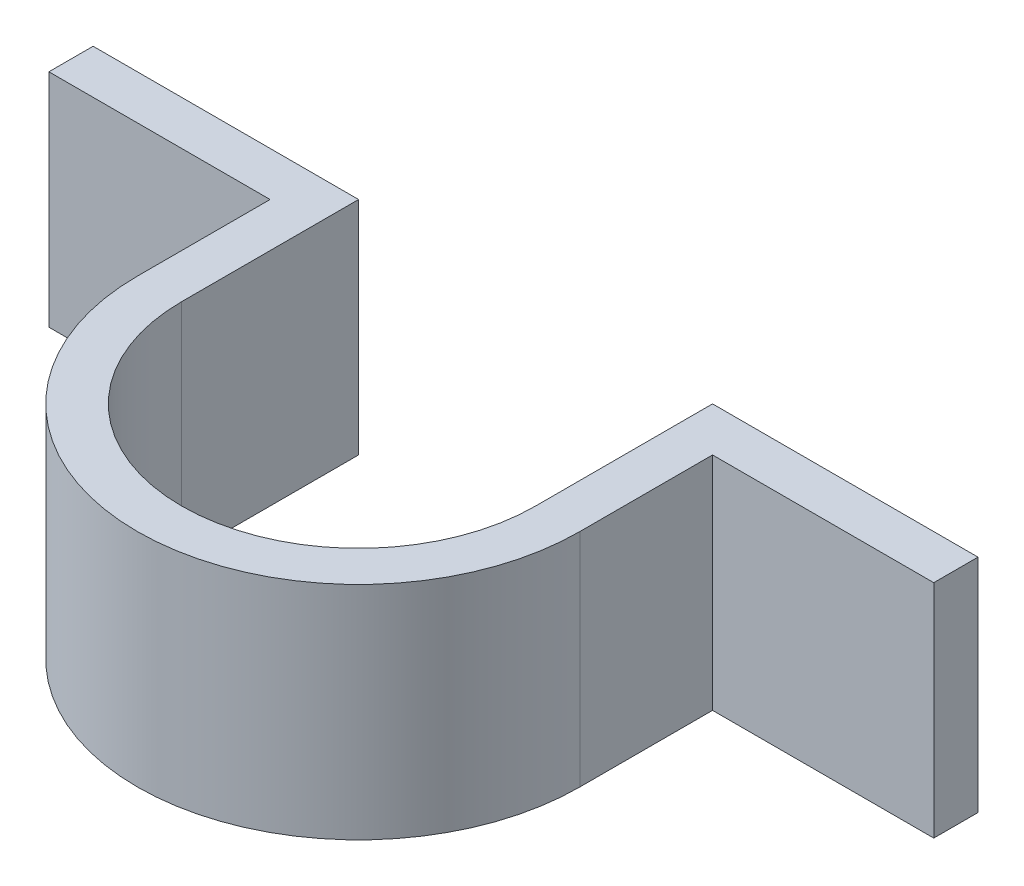
SolidWorks part; units mm, degrees
ref_plane "Front Plane" through (0, 0, 0) normal (0, 0, 1) x (1, 0, 0)
ref_plane "Top Plane" through (0, 0, 0) normal (0, 1, 0) x (1, 0, 0)
ref_plane "Right Plane" through (0, 0, 0) normal (1, 0, 0) x (0, 0, -1)
sketch "Sketch1" plane through (0, 0, 0) normal (0, 1, 0) x (1, 0, 0)
  line L0 (-4, 0) -> (-4, 4)
  line L1 (-4, 4) -> (-10, 4)
  line L6 (-10, 4) -> (-10, 3)
  line L7 (-10, 3) -> (-5, 3)
  line L10 (-5, 3) -> (-5, 0)
  line L11 (4, 0) -> (4, 4)
  line L12 (4, 4) -> (10, 4)
  line L13 (10, 4) -> (10, 3)
  line L14 (10, 3) -> (5, 3)
  line L15 (5, 3) -> (5, 0)
  line L16 (-5, 0) -> (-4, 0) construction
  line L17 (4, 0) -> (-4, 0) construction
  line L18 (5, 0) -> (4, 0) construction
  arc A4 (-4, 0) -> (4, 0) centre (0, 0) ccw
  arc A5 (-5, 0) -> (5, 0) centre (0, 0) ccw
  dimension "D4" = 5
  dimension "D1" = 8
  dimension "D2" = 4
  dimension "D3" = 1
extrude "Boss-Extrude2" add sketch "Sketch1" along normal blind 2.5 and the other way blind 2.5
